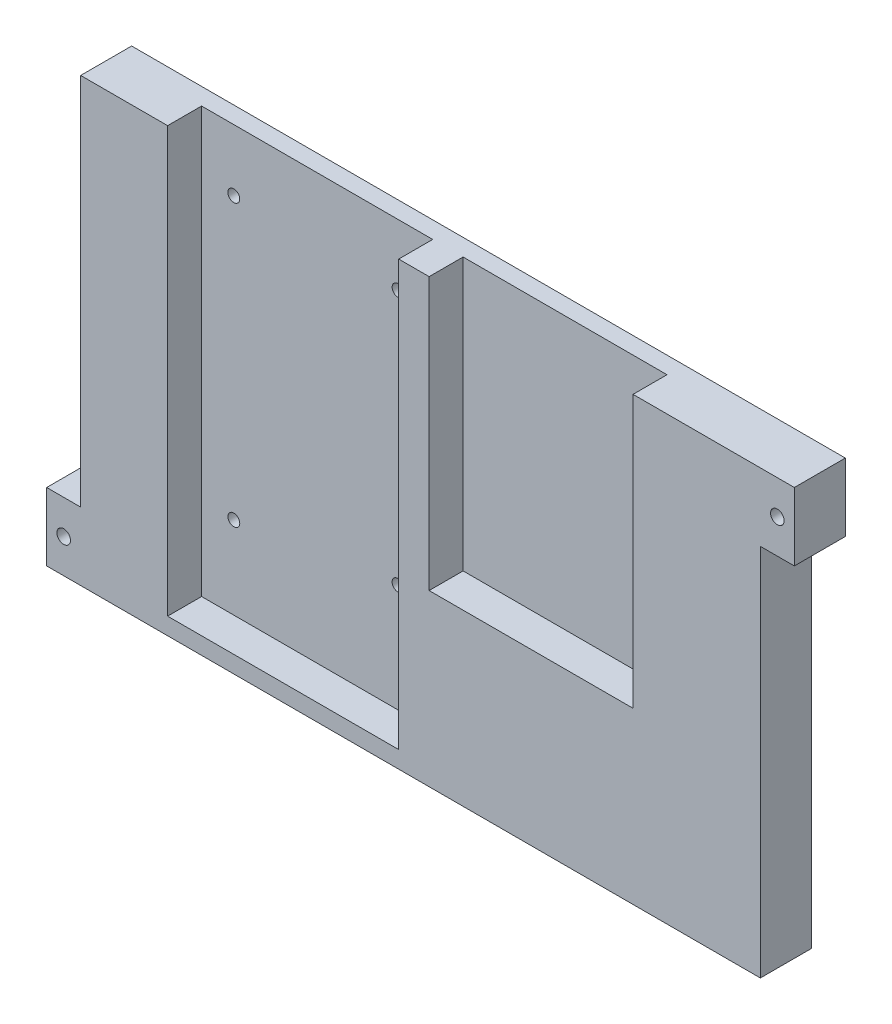
SolidWorks part; units mm, degrees
ref_plane "Front Plane" through (0, 0, 0) normal (0, 0, 1) x (1, 0, 0)
ref_plane "Top Plane" through (0, 0, 0) normal (0, 1, 0) x (1, 0, 0)
ref_plane "Right Plane" through (0, 0, 0) normal (1, 0, 0) x (0, 0, -1)
sketch "Sketch1" plane through (0, 0, 0) normal (0, 0, 1) x (1, 0, 0)
  line L0 (0, 0) -> (200, 0)
  line L1 (0, 0) -> (0, 130)
  line L2 (0, 130) -> (200, 130)
  line L3 (200, 130) -> (200, 0)
  line L4 (100, 130) -> (100, 0)
  point P8 (100, 0)
  dimension "D1" = 200
  dimension "D2" = 200
  dimension "D3" = 130
extrude "Boss-Extrude1" add sketch "Sketch1" along normal blind 15 contours L2 L4 L0 L3 | L4 L2 L1 L0 region at (50, 65, 0) region at (150, 65, 0)
sketch "Sketch2" plane through (0, 0, 15) normal (0, 0, 1) x (1, 0, 0)
  line L0 (0, 130) -> (200, 130) construction
  line L1 (25.584, 130) -> (93.584, 130)
  line L2 (25.584, 130) -> (25.584, 5)
  line L3 (25.584, 5) -> (93.584, 5)
  line L4 (93.584, 130) -> (93.584, 5)
  line L6 (102.5349, 130) -> (162.5349, 130)
  line L7 (102.5349, 130) -> (102.5349, 50)
  line L8 (102.5349, 50) -> (162.5349, 50)
  line L9 (162.5349, 130) -> (162.5349, 50)
  dimension "D1" = 125
  dimension "D2" = 68
  dimension "D3" = 0
  dimension "D4" = 80
  dimension "D5" = 60
extrude "Cut-Extrude1" cut sketch "Sketch2" against normal blind 10
sketch "Sketch3" plane through (0, 0, 5) normal (0, 0, 1) x (1, 0, 0)
  line L1 (25.584, 130) -> (93.584, 130)
  line L2 (25.584, 130) -> (25.584, 5)
  line L3 (25.584, 5) -> (93.584, 5)
  line L4 (93.584, 130) -> (93.584, 5)
  circle A0 centre (35.0631, 111.8946) radius 1.75
  circle A1 centre (83.3993, 111.8946) radius 1.75
  circle A2 centre (35.0631, 29.2684) radius 1.75
  circle A3 centre (83.3993, 36.7614) radius 1.75
  dimension "D1" = 3.5
  dimension "D2" = 3.5
  dimension "D3" = 3.5
  dimension "D4" = 3.5
sketch "Sketch6" plane through (0, 0, 15) normal (0, 0, 1) x (1, 0, 0)
  circle A0 centre (35.0631, 111.8946) radius 1.75
  circle A1 centre (83.3993, 111.8946) radius 1.75
  circle A2 centre (83.3993, 36.7614) radius 1.75
  circle A3 centre (35.0631, 29.2684) radius 1.75
extrude "Cut-Extrude10" cut sketch "Sketch6" against normal blind 15
sketch "Sketch7" plane through (200, 0, 0) normal (1, 0, 0) x (0, 0, -1)
  line L0 (0, 130) -> (0, 0) construction
  line L1 (-15, 130) -> (0, 130)
  line L2 (-15, 130) -> (-15, 110)
  line L3 (-15, 110) -> (0, 110)
  line L4 (0, 130) -> (0, 110)
  dimension "D1" = 20
extrude "Boss-Extrude2" add sketch "Sketch7" along normal blind 10
sketch "Sketch8" plane through (0, 0, 0) normal (-1, 0, 0) x (0, 0, 1)
  line L0 (0, 0) -> (0, 130) construction
  line L1 (0, 20) -> (15, 20)
  line L2 (0, 20) -> (0, 0)
  line L3 (0, 0) -> (15, 0)
  line L4 (15, 20) -> (15, 0)
  dimension "D1" = 20
extrude "Boss-Extrude3" add sketch "Sketch8" along normal blind 10
sketch "Sketch9" plane through (0, 0, 15) normal (0, 0, 1) x (1, 0, 0)
  line L0 (210, 130) -> (210, 110) construction
  line L1 (162.5349, 130) -> (210, 130) construction
  line L2 (-10, 0) -> (-10, 20) construction
  line L3 (-10, 0) -> (200, 0) construction
  circle A0 centre (-5, 10) radius 2
  circle A1 centre (205, 120) radius 2
  dimension "D1" = 4
  dimension "D2" = 4
  dimension "D3" = 5
  dimension "D4" = 10
  dimension "D5" = 5
  dimension "D6" = 10
extrude "Cut-Extrude11" cut sketch "Sketch9" against normal blind 40 and the other way blind 40
